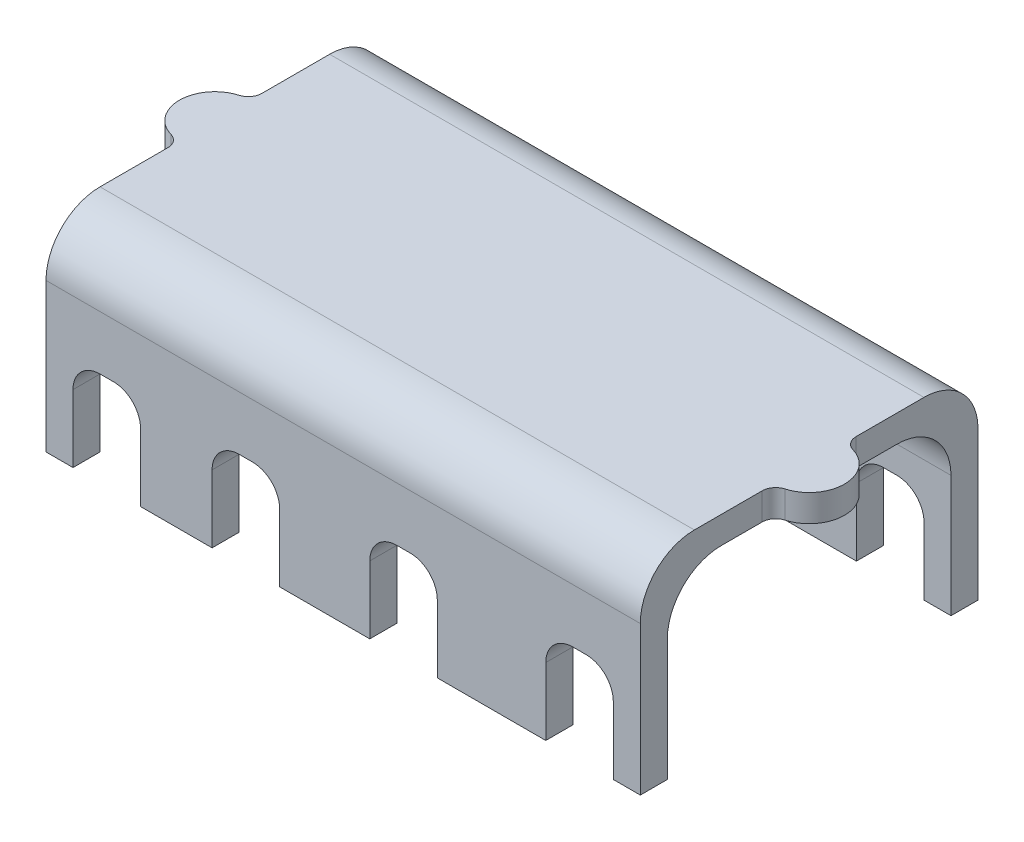
SolidWorks part; units mm, degrees
ref_plane "Plano frontal" through (0, 0, 0) normal (0, 0, 1) x (1, 0, 0)
ref_plane "Plano superior" through (0, 0, 0) normal (0, 1, 0) x (1, 0, 0)
ref_plane "Plano direito" through (0, 0, 0) normal (1, 0, 0) x (0, 0, -1)
sketch "Esboço1" plane through (0, 0, 0) normal (0, 1, 0) x (1, 0, 0)
  line L1 (-22, -12.5) -> (22, -12.5)
  line L2 (-22, -12.5) -> (-22, 12.5)
  line L3 (-22, 12.5) -> (22, 12.5)
  line L4 (22, -12.5) -> (22, 12.5)
  line L5 (-22, -12.5) -> (22, 12.5) construction
  line L6 (-22, 12.5) -> (22, -12.5) construction
  point P0 (0, 0)
  dimension "D1" = 44
  dimension "D2" = 25
extrude "Ressalto-extrusão1" add sketch "Esboço1" along normal mid plane 15
shell "Casca1" thickness 2 removed face at (0, -7.5, 0) removed face at (-22, 0, 0) removed face at (22, 0, 0)
sketch "Esboço2" plane through (0, 0, 12.5) normal (0, 0, 1) x (1, 0, 0)
  line L0 (22, 7.5) -> (22, -7.5) construction
  line L5 (-9.7033, -14.5) -> (-4.7033, -14.5)
  line L6 (-9.7033, -14.5) -> (-9.7033, -0.5)
  line L7 (-22, -7.5) -> (22, -7.5) construction
  line L8 (-20, -14.5) -> (-15, -14.5)
  line L9 (-20, -14.5) -> (-20, -0.5)
  line L10 (-20, -0.5) -> (-15, -0.5)
  line L11 (-15, -14.5) -> (-15, -0.5)
  line L12 (-20, -14.5) -> (-15, -0.5) construction
  line L13 (-20, -0.5) -> (-15, -14.5) construction
  line L14 (-22, 7.5) -> (-22, -7.5) construction
  line L15 (-9.7033, -0.5) -> (-4.7033, -0.5)
  line L16 (-4.7033, -14.5) -> (-4.7033, -0.5)
  line L17 (-9.7033, -14.5) -> (-4.7033, -0.5) construction
  line L18 (-9.7033, -0.5) -> (-4.7033, -14.5) construction
  line L19 (1.9702, -14.5) -> (6.9702, -14.5)
  line L20 (1.9702, -14.5) -> (1.9702, -0.5)
  line L21 (1.9702, -0.5) -> (6.9702, -0.5)
  line L22 (6.9702, -14.5) -> (6.9702, -0.5)
  line L23 (1.9702, -14.5) -> (6.9702, -0.5) construction
  line L24 (1.9702, -0.5) -> (6.9702, -14.5) construction
  line L25 (15, -14.5) -> (20, -14.5)
  line L26 (15, -14.5) -> (15, -0.5)
  line L27 (15, -0.5) -> (20, -0.5)
  line L28 (20, -14.5) -> (20, -0.5)
  line L29 (15, -14.5) -> (20, -0.5) construction
  line L30 (15, -0.5) -> (20, -14.5) construction
  point P0 (-17.5, -7.5)
  point P9 (-7.2033, -7.5)
  point P14 (4.4702, -7.5)
  point P19 (17.5, -7.5)
  dimension "D2" = 5
  dimension "D3" = 7
  dimension "D1" = 2
  dimension "D4" = 2
extrude "Corte-extrusão1" cut sketch "Esboço2" against normal through all
fillet "Filete1" radius 2 16 edges at (15, -0.5, 11.5) (15, -0.5, -11.5) (20, -0.5, 11.5) (20, -0.5, -11.5) (1.9702, -0.5, 11.5) (1.9702, -0.5, -11.5) (6.9702, -0.5, 11.5) (6.9702, -0.5, -11.5) (-9.7033, -0.5, 11.5) (-9.7033, -0.5, -11.5) (-4.7033, -0.5, 11.5) (-4.7033, -0.5, -11.5) (-15, -0.5, 11.5) (-15, -0.5, -11.5) (-20, -0.5, -11.5) (-20, -0.5, 11.5)
fillet "Filete2" radius 4 4 edges at (0, 7.5, -12.5) (0, 7.5, 12.5) (0, 5.5, 10.5) (0, 5.5, -10.5)
sketch "Esboço5" plane through (0, 7.5, 0) normal (0, 1, 0) x (1, 0, 0)
  line L0 (-22, -1.619) -> (-22, -2.619)
  line L1 (-22, -2.619) -> (-22, -1.619)
  line L2 (-22, 1.619) -> (-22, 2.619)
  line L3 (-22, 8.5) -> (-22, -8.5) construction
  line L4 (-22, -1.619) -> (-22, 1.619)
  line L5 (0, -8.25) -> (0, 8.25) construction
  line L6 (22, -1.619) -> (22, 1.619)
  line L7 (22, 1.619) -> (22, 2.619)
  line L8 (22, -2.619) -> (22, -1.619)
  line L9 (22, -1.619) -> (22, -2.619)
  arc A0 (-22, 2.619) -> (-22, -2.619) centre (-22, 0) ccw
  arc A2 (22, 2.619) -> (22, -2.619) centre (22, 0) cw
extrude "Ressalto-extrusão4" add sketch "Esboço5" against normal up to surface (2 mm away) separate body up to face at (0, 5.5, 0)
combine bodies "Combinar1" operation type add bodies to combine 102 108 110
sketch "Esboço3" [suppressed] plane through (-22, 0, 0) normal (1, 0, 0) x (0, 0, -1)
  line L0 (10.5, -7.5) -> (8.5, -7.5)
  line L2 (12.5, -8.5) -> (12.5, -7.5)
  line L3 (0, 5.5) -> (0, -5.9035) construction
  line L4 (6.5, 5.5) -> (-6.5, 5.5) construction
  line L8 (10.5, -7.5) -> (12.5, -7.5)
  line L10 (8.5, -7.5) -> (8.5, -8)
  line L11 (8.5, -8) -> (12.5, -8.5)
  line L12 (-8.5, -8) -> (-12.5, -8.5)
  line L13 (-8.5, -7.5) -> (-8.5, -8)
  line L14 (-10.5, -7.5) -> (-12.5, -7.5)
  line L15 (-12.5, -8.5) -> (-12.5, -7.5)
  line L16 (-10.5, -7.5) -> (-8.5, -7.5)
  dimension "D1" = 2
  dimension "D2" = 1
  dimension "D3" = 0.5
fillet "Filete4" radius 1 4 edges at (-22, 6.5, -2.619) (-22, 6.5, 2.619) (22, 6.5, -2.619) (22, 6.5, 2.619)
move or copy body "Corpo-Converter em corpo de malha1" [suppressed] bodies to move or copy 109 copy no translate (0, 0, 0) parameters "D1"=0, "D2"=0, "D3"=0
